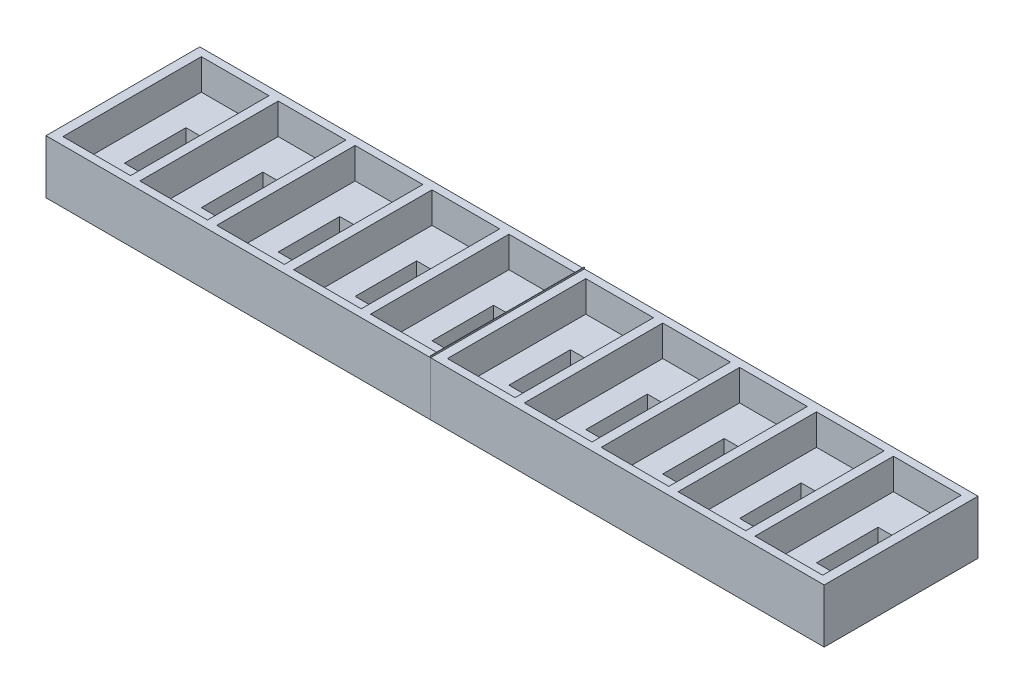
SolidWorks part; units mm, degrees
ref_plane "Front Plane" through (0, 0, 0) normal (0, 0, 1) x (1, 0, 0)
ref_plane "Top Plane" through (0, 0, 0) normal (0, 1, 0) x (1, 0, 0)
ref_plane "Right Plane" through (0, 0, 0) normal (1, 0, 0) x (0, 0, -1)
sketch "Sketch1" plane through (0, 0, 0) normal (0, 1, 0) x (1, 0, 0)
  line L1 (0, 0) -> (253, 0)
  line L2 (0, 0) -> (0, -50)
  line L3 (0, -50) -> (253, -50)
  line L4 (253, 0) -> (253, -50)
  point P5 (0, 0)
extrude "Boss-Extrude1" add sketch "Sketch1" along normal blind 17.5
sketch "Sketch2" plane through (0, 17.5, 0) normal (0, 1, 0) x (1, 0, 0)
  line L1 (3, -2.5) -> (25, -2.5)
  line L2 (3, -2.5) -> (3, -47.5)
  line L3 (3, -47.5) -> (25, -47.5)
  line L4 (25, -2.5) -> (25, -47.5)
  point P4 (0, 0)
extrude "Cut-Extrude1" cut sketch "Sketch2" against normal blind 10
sketch "Sketch3" plane through (0, 17.5, 0) normal (0, 1, 0) x (1, 0, 0)
  line L1 (10.5, -15) -> (25, -15)
  line L2 (10.5, -15) -> (10.5, -35)
  line L3 (10.5, -35) -> (25, -35)
  line L4 (25, -15) -> (25, -35)
extrude "Cut-Extrude2" cut sketch "Sketch3" against normal blind 17.5
pattern_linear "LPattern1" count 10 spacing 25 along (1, 0, 0) of "Cut-Extrude1", "Cut-Extrude2"
ref_plane "Plane1" through (125, 0, 0) normal (-1, 0, 0) x (0, 0, 1)
sketch "Sketch4" plane through (125, 0, 0) normal (-1, 0, 0) x (0, 0, 1)
  line L1 (0, 18) -> (50, 18)
  line L2 (0, 18) -> (0, 0)
  line L3 (0, 0) -> (50, 0)
  line L4 (50, 18) -> (50, 0)
  point P6 (0, 0)
  point P7 (0, 0)
extrude "Boss-Extrude2" add sketch "Sketch4" along normal mid plane 0.1
split "Split1" bodies to split 106 resulting bodies 107 108 split by face at (125.05, 17.75, 25)
